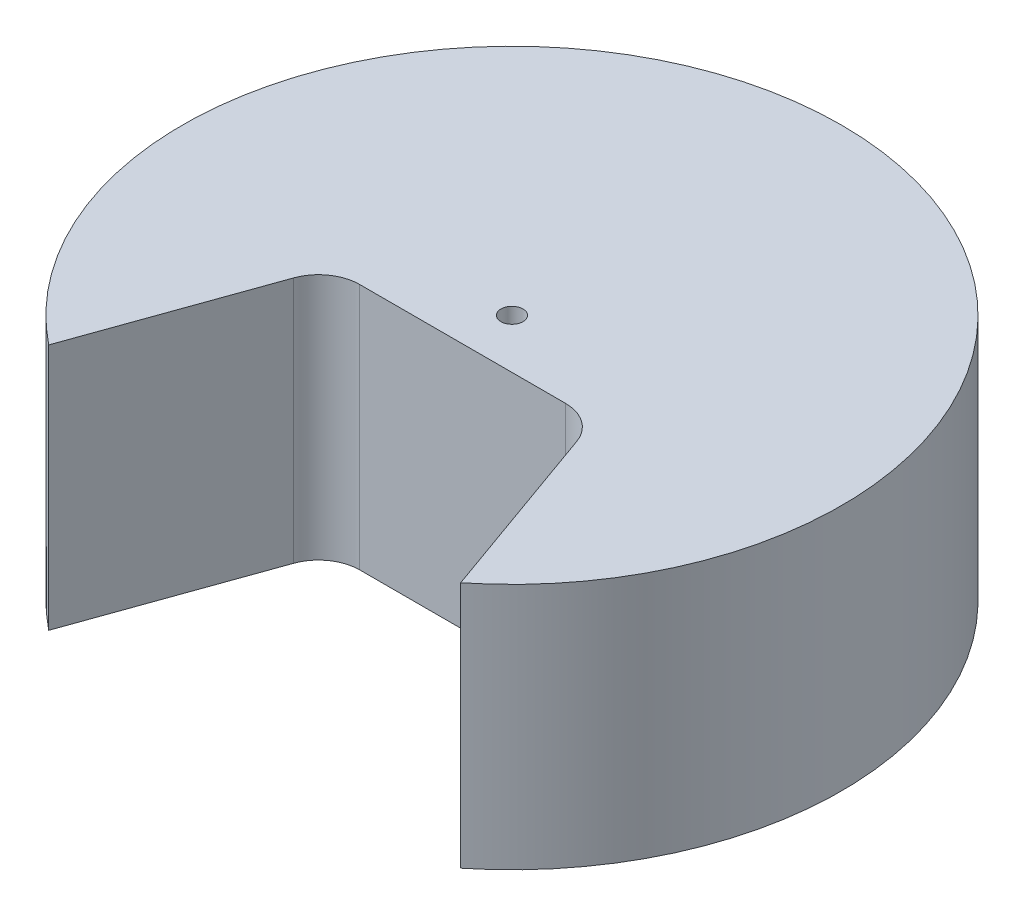
SolidWorks part; units mm, degrees
ref_plane "Front Plane" through (0, 0, 0) normal (0, 0, 1) x (1, 0, 0)
ref_plane "Top Plane" through (0, 0, 0) normal (0, 1, 0) x (1, 0, 0)
ref_plane "Right Plane" through (0, 0, 0) normal (1, 0, 0) x (0, 0, -1)
sketch "Sketch1" plane through (0, 0, 0) normal (0, 1, 0) x (1, 0, 0)
  circle A0 centre (0, 0) radius 50.8
  dimension "D1" = 101.6
extrude "Boss-Extrude1" add sketch "Sketch1" along normal blind 38.1
sketch "Sketch2" plane through (0, 38.1, 0) normal (0, 1, 0) x (1, 0, 0)
  line L0 (31.75, -39.6557) -> (20.32, -7.62)
  line L1 (-20.32, -7.62) -> (20.32, -7.62)
  line L2 (-31.75, -39.6557) -> (-31.75, -50.8)
  line L3 (-31.75, -50.8) -> (31.75, -50.8)
  line L4 (31.75, -39.6557) -> (31.75, -50.8)
  line L5 (0, -20.955) -> (0, 20.955) construction
  line L6 (-31.75, -39.6557) -> (-20.32, -7.62)
  circle A1 centre (0, 0) radius 50.8 construction
  dimension "D1" = 7.62
  dimension "D2" = 31.75
  dimension "D3" = 20.32
extrude "Cut-Extrude1" cut sketch "Sketch2" against normal up to next
fillet "Fillet1" radius 6.35 2 edges at (20.32, 19.05, 7.62) (-20.32, 19.05, 7.62)
hole_wizard "M3 Clearance Hole1" positions "Sketch4" profile "Sketch5" hole size "M3" standard "ANSI Metric" end condition through all
sketch "Sketch4" plane through (0, 38.1, 0) normal (0, 1, 0) x (1, 0, 0)
  point P0 (0, 0)
sketch "Sketch5" plane through (0, 38.1, 0) normal (1, 0, 0) x (0, 0, 1)
  line L0 (0, 0) -> (0, 38.1)
  line L1 (0, 38.1) -> (1.7, 38.1)
  line L2 (1.7, 38.1) -> (1.7, 0)
  line L5 (1.7, 0) -> (0, 0)
  line L11 (0, -6.35) -> (0, 107.95) construction
  dimension "Thru Hole Dia." = 3.4
  dimension "Thru Hole Depth" = 38.1
ref_axis "Axis1" through (0, 0, 0) along (0, 1, 0)
